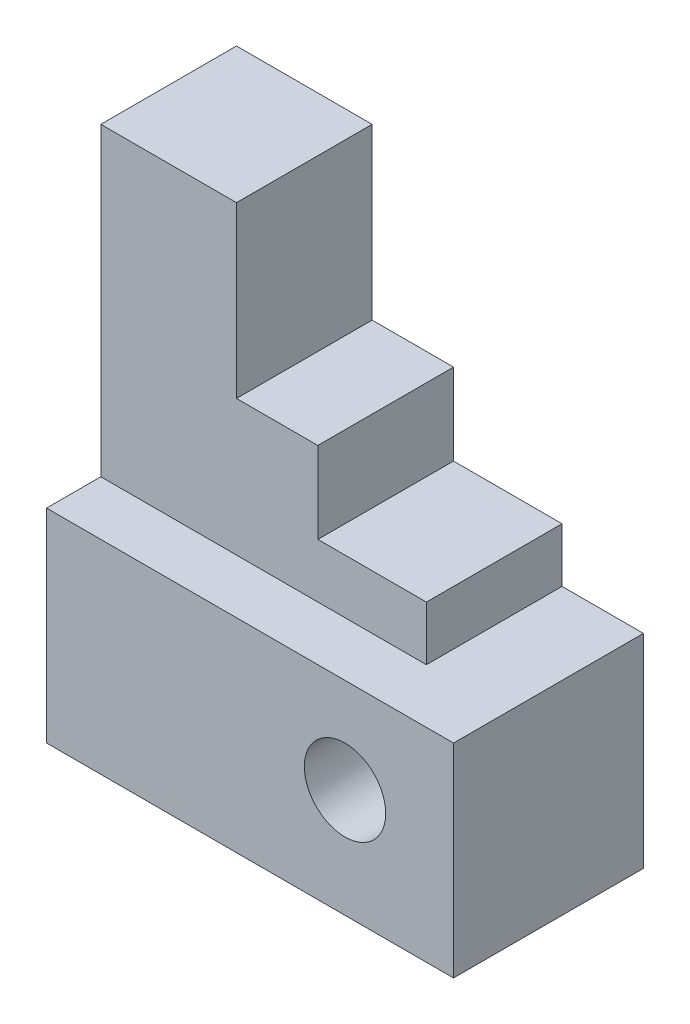
SolidWorks part; units mm, degrees
material "Aluminum Bronze"
ref_plane "Front Plane" through (0, 0, 0) normal (0, 0, 1) x (1, 0, 0)
ref_plane "Top Plane" through (0, 0, 0) normal (0, 1, 0) x (1, 0, 0)
ref_plane "Right Plane" through (0, 0, 0) normal (1, 0, 0) x (0, 0, -1)
sketch "Sketch1" plane through (0, 0, 0) normal (0, 0, 1) x (1, 0, 0)
  line L1 (0, 0) -> (60, 0)
  line L2 (0, 0) -> (0, 30)
  line L3 (0, 30) -> (60, 30)
  line L4 (60, 0) -> (60, 30)
  circle A0 centre (44, 16) radius 6
  dimension "D3" = 12
  dimension "D1" = 60
  dimension "D2" = 30
  dimension "D4" = 16
  dimension "D5" = 16
extrude "Boss-Extrude1" add sketch "Sketch1" along normal blind 28
sketch "Sketch2" plane through (0, 0, 0) normal (0, 0, 1) x (1, 0, 0)
  line L0 (0, 30) -> (0, 75)
  line L1 (0, 75) -> (20, 75)
  line L2 (20, 75) -> (20, 50)
  line L3 (20, 50) -> (32, 50)
  line L4 (32, 50) -> (32, 38)
  line L5 (32, 38) -> (48, 38)
  line L6 (48, 38) -> (48, 30)
  line L7 (60, 30) -> (0, 30) construction
  line L8 (48, 30) -> (0, 30)
  line L9 (0, 0) -> (60, 0) construction
  line L10 (60, 0) -> (60, 30) construction
  dimension "D1" = 75
  dimension "D2" = 12
  dimension "D3" = 12
  dimension "D4" = 12
  dimension "D5" = 20
  dimension "D6" = 20
extrude "Boss-Extrude2" add sketch "Sketch2" along normal blind 20
